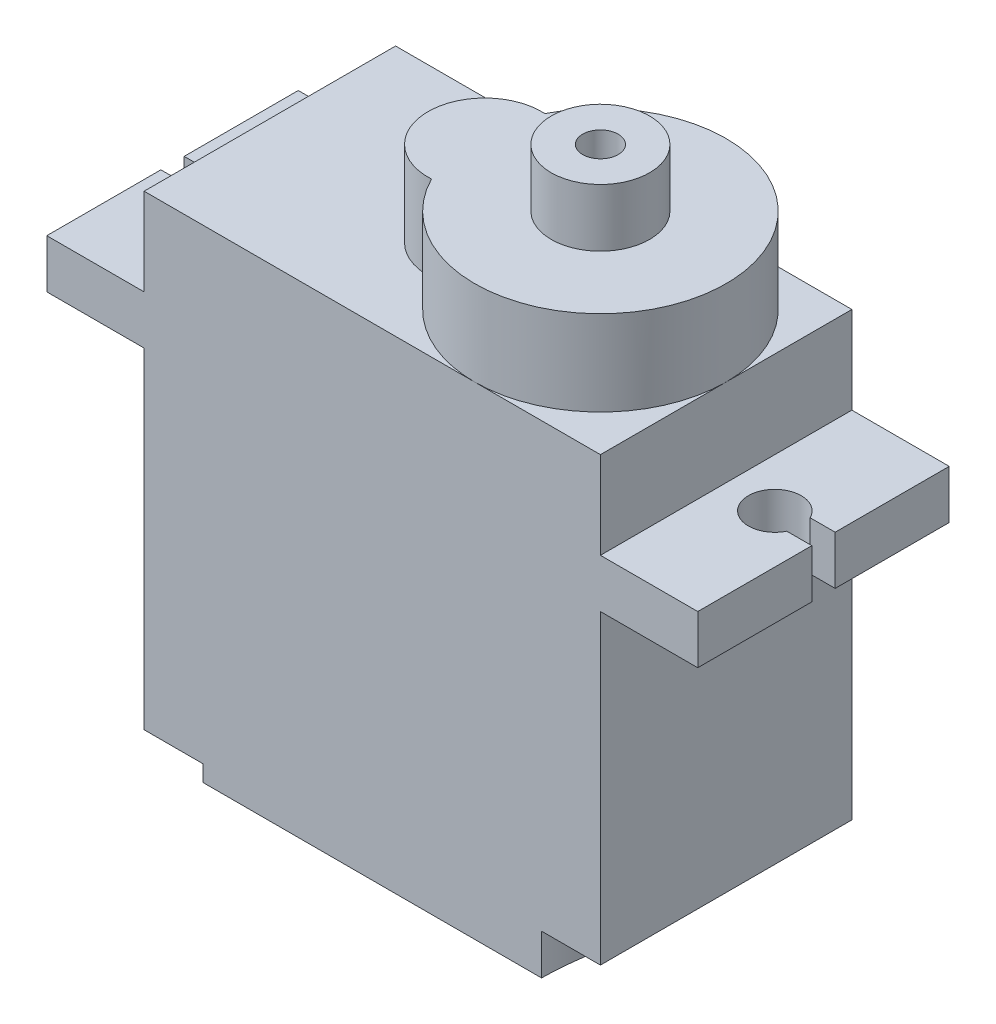
SolidWorks part; units mm, degrees
ref_plane "Alzado" through (0, 0, 0) normal (0, 0, 1) x (1, 0, 0)
ref_plane "Planta" through (0, 0, 0) normal (0, 1, 0) x (1, 0, 0)
ref_plane "Vista lateral" through (0, 0, 0) normal (1, 0, 0) x (0, 0, -1)
sketch "Croquis1" plane through (0, 0, 0) normal (0, 0, 1) x (1, 0, 0)
  line L0 (0, 11.9) -> (0, -11.9) construction
  line L4 (-11.25, -11.9) -> (-11.25, 11.9)
  line L5 (-11.25, 11.9) -> (11.25, 11.9)
  line L6 (-11.25, -11.9) -> (11.25, -11.9)
  line L7 (-16.05, 5.2) -> (-11.25, 5.2)
  line L8 (-16.05, 5.2) -> (-16.05, 7.6)
  line L9 (-16.05, 7.6) -> (-11.25, 7.6)
  line L10 (-11.25, 5.2) -> (-11.25, 7.6)
  line L11 (-16.05, 5.2) -> (-11.25, 7.6) construction
  line L12 (-16.05, 7.6) -> (-11.25, 5.2) construction
  line L14 (11.25, -11.9) -> (11.25, 11.9)
  line L16 (16.05, 7.6) -> (11.25, 7.6)
  line L17 (11.25, 5.2) -> (11.25, 7.6)
  line L18 (16.05, 5.2) -> (11.25, 5.2)
  line L19 (16.05, 5.2) -> (16.05, 7.6)
  point P0 (0, 0)
  point P2 (-11.25, 0)
  point P6 (-13.65, 6.4)
  dimension "D1" = 23.8
  dimension "D2" = 2.4
  dimension "D3" = 22.5
  dimension "D4" = 4.8
  dimension "D5" = 4.3
extrude "Saliente-Extruir1" add sketch "Croquis1" along normal mid plane 12.4 contours L9 L8 L7 L4 | L6 L14 L5 L4 | L18 L19 L16 L14 region at (0, 0, 0) region at (-13.65, 6.4, 0) region at (13.65, 6.4, 0)
sketch "Croquis2" plane through (0, 11.9, 0) normal (0, 1, 0) x (1, 0, 0)
  line L0 (-11.25, 6.2) -> (11.25, 6.2) construction
  line L1 (-11.25, -6.2) -> (11.25, -6.2) construction
  line L2 (11.25, -6.2) -> (11.25, 6.2) construction
  line L3 (-0.65, 0) -> (-3.45, 0) construction
  arc A0 (-0.4842, -2.7951) -> (-0.4842, 2.7951) centre (5.05, 0) ccw
  arc A1 (-0.4842, 2.7951) -> (-0.4842, -2.7951) centre (-0.65, 0) ccw
  dimension "D2" = 5.6
  dimension "D1" = 14.7
extrude "Saliente-Extruir2" add sketch "Croquis2" along normal blind 4.2
sketch "Croquis3" plane through (0, 7.6, 0) normal (0, 1, 0) x (1, 0, 0)
  line L0 (0, -6.2) -> (0, 6.2) construction
  line L1 (-11.25, -6.2) -> (5.05, -6.2) construction
  line L2 (-11.25, 6.2) -> (5.05, 6.2) construction
  line L3 (16.05, 0.575) -> (14.8159, 0.575)
  line L4 (16.05, -6.2) -> (16.05, 6.2) construction
  line L5 (16.05, -0.575) -> (14.8159, -0.575)
  line L6 (16.05, 0.575) -> (16.05, -0.575)
  line L7 (-16.05, 0.575) -> (-14.8159, 0.575)
  line L8 (-16.05, 0.575) -> (-16.05, -0.575)
  line L9 (-16.05, -0.575) -> (-14.8159, -0.575)
  arc A1 (14.8159, 0.575) -> (14.8159, -0.575) centre (13.65, 0) ccw
  arc A2 (-14.8159, 0.575) -> (-14.8159, -0.575) centre (-13.65, 0) cw
  point P16 (16.05, 0)
  point P18 (16.05, 0)
  dimension "D2" = 2.6
  dimension "D1" = 1.15
  dimension "D3" = 2.4
extrude "Cortar-Extruir1" cut sketch "Croquis3" against normal up to next
sketch "Croquis4" plane through (0, -11.9, 0) normal (0, -1, 0) x (1, 0, 0)
  line L0 (0, 6.2) -> (0, -6.2) construction
  line L1 (-11.25, 0) -> (11.25, 0) construction
  line L2 (-11.25, 3.3) -> (-11.25, 6.2)
  line L3 (-11.25, 6.2) -> (-8.35, 6.2)
  line L4 (-11.25, -6.2) -> (11.25, -6.2)
  line L5 (11.25, -6.2) -> (11.25, 6.2)
  line L6 (11.25, 6.2) -> (-11.25, 6.2)
  line L7 (-11.25, 6.2) -> (-11.25, -6.2)
  line L8 (-11.25, -6.2) -> (11.25, -6.2)
  line L9 (11.25, -6.2) -> (11.25, 6.2)
  line L10 (11.25, 6.2) -> (-11.25, 6.2)
  line L11 (-11.25, 6.2) -> (-11.25, -6.2)
  line L12 (-11.25, -3.3) -> (-11.25, -6.2)
  line L13 (-11.25, -6.2) -> (-8.35, -6.2)
  line L14 (11.25, 3.3) -> (11.25, 6.2)
  line L15 (11.25, 6.2) -> (8.35, 6.2)
  line L16 (11.25, -3.3) -> (11.25, -6.2)
  line L17 (11.25, -6.2) -> (8.35, -6.2)
  line L18 (8.35, 6.2) -> (8.35, -6.2)
  line L19 (9.75, -1.875) -> (11.25, -1.875)
  line L20 (9.75, -1.875) -> (9.75, 1.875)
  line L21 (9.75, 1.875) -> (11.25, 1.875)
  line L22 (11.25, -1.875) -> (11.25, 1.875)
  line L23 (9.75, -1.875) -> (11.25, 1.875) construction
  line L24 (9.75, 1.875) -> (11.25, -1.875) construction
  arc A0 (-8.35, 6.2) -> (-11.25, 3.3) centre (-11.25, 6.2) cw
  arc A1 (-8.35, -6.2) -> (-11.25, -3.3) centre (-11.25, -6.2) ccw
  arc A2 (8.35, 6.2) -> (11.25, 3.3) centre (11.25, 6.2) ccw
  arc A3 (8.35, -6.2) -> (11.25, -3.3) centre (11.25, -6.2) cw
  point P17 (10.5, 0)
  dimension "D2" = 2.9
  dimension "D3" = 3.75
  dimension "D4" = 1.5
  dimension "D1" = 0
extrude "Cortar-Extruir3" cut sketch "Croquis4" against normal blind 0.8 contours A0 L16 L4 | L17 A1 L11 region at (-10.0192, -11.9, 4.9692) region at (-10.0192, -11.9, -4.9692)
extrude "Cortar-Extruir4" cut sketch "Croquis4<5>" against normal blind 2 contours L16 A2 L9 | L21 L20 L19 A3 | A3 L17 region at (10.0192, -11.9, 4.9692) region at (10.0192, -11.9, -4.9692) region at (10.5, -11.9, 0)
sketch "Croquis4<5>" plane through (0, -11.9, 0) normal (0, -1, 0) x (1, 0, 0) same geometry as "Croquis4"
sketch "Croquis6" plane through (0, 0, -6.2) normal (0, 0, -1) x (-1, 0, 0)
  line L0 (-11.25, -9.9) -> (-8.35, -11.9)
  line L1 (-8.35, -11.9) -> (-11.25, -11.9)
  line L2 (-11.25, -11.9) -> (-11.25, -9.9)
extrude "Cortar-Extruir5" cut sketch "Croquis6" against normal through all
sketch "Croquis7" plane through (0, 16.1, 0) normal (0, 1, 0) x (1, 0, 0)
  circle A0 centre (5.05, 0) radius 2.425
  circle A1 centre (5.05, 0) radius 0.875
  dimension "D1" = 4.85
  dimension "D2" = 1.55
extrude "Saliente-Extruir4" add sketch "Croquis7" along normal blind 2.85
sketch "Sketch3" plane through (0, 18.95, 0) normal (0, 1, 0) x (1, 0, 0)
  line L0 (-3.4533, 0) -> (11.25, 0)
  circle A0 centre (5.05, 0) radius 2.425
  circle A1 centre (5.05, 0) radius 6.2
  circle A2 centre (-0.6461, 0) radius 2.8072
  dimension "D2" = 5.6143
  dimension "D4" = 12.4
  dimension "D1" = 14.7033
  dimension "D3" = 5.6961
